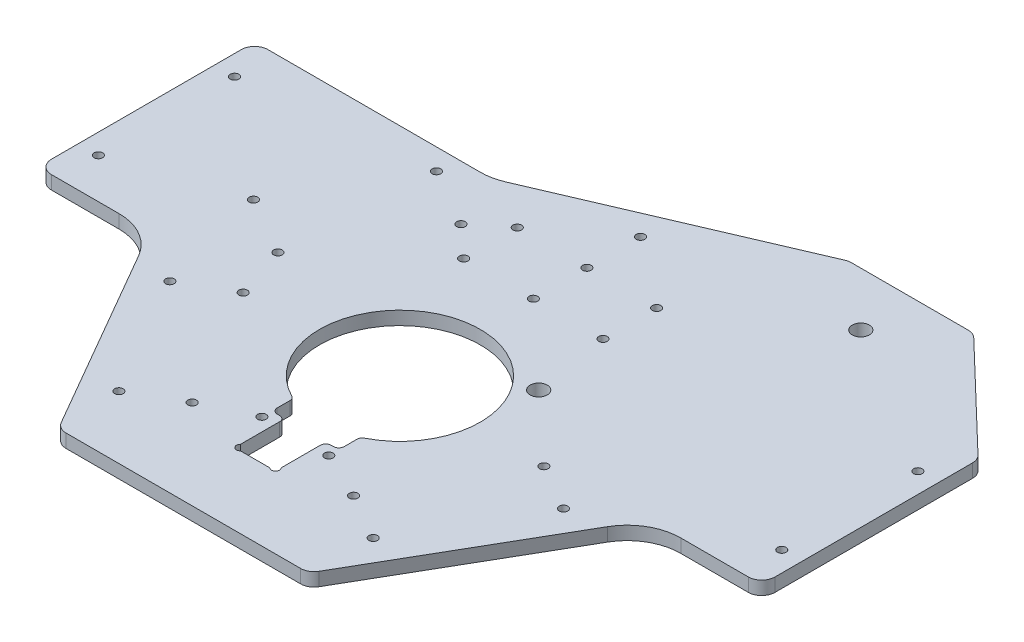
SolidWorks part; units mm, degrees
material "Acrylic (Medium-high impact)"
ref_plane "Front Plane" through (0, 0, 0) normal (0, 0, 1) x (1, 0, 0)
ref_plane "Top Plane" through (0, 0, 0) normal (0, 1, 0) x (1, 0, 0)
ref_plane "Right Plane" through (0, 0, 0) normal (1, 0, 0) x (0, 0, -1)
sketch "Sketch1" plane through (0, 0, 0) normal (0, 1, 0) x (1, 0, 0)
  line L0 (0, 0) -> (0, 59.7887) construction
  line L1 (88.7366, -45.4586) -> (19.8205, -5.6699) construction
  line L2 (-5, 99.5775) -> (5, 99.5775) construction
  line L3 (-5, 99.5775) -> (-5, 20) construction
  line L4 (-5, 20) -> (5, 20) construction
  line L5 (5, 99.5775) -> (5, 20) construction
  line L6 (-5, 99.5775) -> (5, 20) construction
  line L7 (-5, 20) -> (5, 99.5775) construction
  line L8 (88.7366, -45.4586) -> (83.7366, -54.1189) construction
  line L9 (83.7366, -54.1189) -> (14.8205, -14.3301) construction
  line L10 (19.8205, -5.6699) -> (14.8205, -14.3301) construction
  line L11 (-83.7366, -54.1189) -> (-14.8205, -14.3301) construction
  line L12 (-83.7366, -54.1189) -> (-88.7366, -45.4586) construction
  line L13 (-88.7366, -45.4586) -> (-19.8205, -5.6699) construction
  line L14 (-14.8205, -14.3301) -> (-19.8205, -5.6699) construction
  line L15 (-5, 59.7887) -> (-120, 59.7887) construction
  line L16 (-49.2786, -34.2245) -> (8.2214, -133.8174) construction
  line L23 (54.2786, -25.5642) -> (111.7786, 74.0287) construction
  circle A0 centre (0, 0) radius 20 construction
  circle A1 centre (-12.5, -19.3067) radius 3 construction
  circle A2 centre (12.5, -19.3067) radius 3 construction
  point P19 (0, 0)
  dimension "D1" = 40
  dimension "D6" = 6
  dimension "D7" = 25
  dimension "D2" = 79.5775
  dimension "D3" = 10
  dimension "D5" = 115
  dimension "D4" = 3
sketch "Sketch2" plane through (0, 0, 0) normal (0, 1, 0) x (1, 0, 0)
  line L0 (-5, 20) -> (5, 99.5775) construction
  line L1 (-26, 49.7887) -> (26, 49.7887) construction
  line L2 (-26, 49.7887) -> (-26, 69.7887) construction
  line L3 (-26, 69.7887) -> (26, 69.7887) construction
  line L4 (26, 49.7887) -> (26, 69.7887) construction
  line L5 (-26, 49.7887) -> (26, 69.7887) construction
  line L6 (-26, 69.7887) -> (26, 49.7887) construction
  line L8 (46.6434, 80.7887) -> (-46.6434, 80.7887)
  line L9 (-46.6434, 80.7887) -> (-93.2868, 0)
  line L10 (-93.2868, 0) -> (-46.6434, -80.7887)
  line L11 (-46.6434, -80.7887) -> (46.6434, -80.7887)
  line L12 (46.6434, -80.7887) -> (93.2868, 0)
  line L13 (93.2868, 0) -> (46.6434, 80.7887)
  circle A0 centre (26, 69.7887) radius 1.6
  circle A1 centre (26, 49.7887) radius 1.6
  circle A2 centre (-26, 49.7887) radius 1.6
  circle A3 centre (-26, 69.7887) radius 1.6
  circle A4 centre (0, 0) radius 30
  circle A5 centre (0, 0) radius 80.7887 construction
  circle A6 centre (56.1183, -2.3777) radius 1.6
  circle A7 centre (73.4388, -12.3777) radius 1.6
  circle A8 centre (47.4388, -57.411) radius 1.6
  circle A9 centre (30.1183, -47.411) radius 1.6
  circle A10 centre (-30.1183, -47.411) radius 1.6
  circle A11 centre (-47.4388, -57.411) radius 1.6
  circle A12 centre (-73.4388, -12.3777) radius 1.6
  circle A13 centre (-56.1183, -2.3777) radius 1.6
  point P0 (0, 59.7887)
  point P39 (0, 0)
  dimension "D3" = 3.2
  dimension "D4" = 60
  dimension "D5" = 11
  dimension "D1" = 52
  dimension "D2" = 20
  dimension "D6" = 3
extrude "Boss-Extrude1" add sketch "Sketch2" along normal blind 5
sketch "Sketch3" plane through (0, 0, 0) normal (0, 1, 0) x (1, 0, 0)
  line L0 (18, 80.7887) -> (18, 24) construction
  line L1 (46.6434, 80.7887) -> (-46.6434, 80.7887) construction
  line L2 (5, 99.5775) -> (5, 20) construction
  line L3 (85.9256, 92.2887) -> (41.3253, 15.0387) construction
  line L5 (26, 49.7887) -> (30.5, 49.7887) construction
  line L6 (30.5, 33.7887) -> (30.5, 49.7887) construction
  line L8 (46.6434, 120.7887) -> (93.2868, 120.7887)
  line L9 (93.2868, 120.7887) -> (93.2868, 0)
  line L14 (93.2868, 0) -> (46.6434, 80.7887) construction
  line L15 (93.2868, 0) -> (46.6434, 80.7887)
  line L16 (-46.6434, 80.7887) -> (46.6434, 120.7887)
  line L17 (46.6434, 120.7887) -> (46.6434, 80.7887) construction
  line L18 (46.6434, 80.7887) -> (-46.6434, 80.7887)
  line L19 (46.6434, -80.7887) -> (93.2868, 0) construction
  circle A0 centre (0, 0) radius 30 construction
  circle A1 centre (30.5, 21.2887) radius 12.5 construction
  circle A5 centre (71.2032, 100.7887) radius 3.2
  circle A6 centre (71.2032, 100.7887) radius 20 construction
  circle A7 centre (71.2032, 100.7887) radius 17 construction
  point P19 (85.9256, 92.2887)
  point P32 (69.9651, 120.7887)
  dimension "D2" = 25
  dimension "D3" = 16
  dimension "D4" = 6.4
  dimension "D5" = 20
  dimension "D6" = 34
  dimension "D1" = 13
extrude "Boss-Extrude2" add sketch "Sketch3" along normal up to surface (5 mm away) up to face at (-30.1183, 5, 49.011)
sketch "Sketch4" plane through (0, 5, 0) normal (0, 1, 0) x (1, 0, 0)
  circle A0 centre (30.5, 21.2887) radius 3.2
  dimension "D1" = 6.4
extrude "Cut-Extrude1" cut sketch "Sketch4" against normal through all
sketch "Sketch5" plane through (0, 5, 0) normal (0, 1, 0) x (1, 0, 0)
  line L4 (-7.6, -29.0214) -> (7.6, -29.0214)
  line L5 (-7.6, -29.0214) -> (-7.6, -54.0214)
  line L6 (-7.6, -54.0214) -> (7.6, -54.0214)
  line L7 (7.6, -29.0214) -> (7.6, -54.0214)
  circle A2 centre (0, 0) radius 30 construction
  dimension "D1" = 15.2
  dimension "D2" = 25
extrude "Cut-Extrude2" cut sketch "Sketch5" against normal through all
sketch "Sketch7" plane through (0, 0, 0) normal (0, -1, 0) x (1, 0, 0)
  line L0 (0, 0) -> (0, 39.0214) construction
  line L1 (0, 39.0214) -> (12.5, 39.0214) construction
  line L2 (0, 39.0214) -> (-12.5, 39.0214) construction
  line L3 (-7.6, 52.9607) -> (-6.5393, 52.9607) construction
  line L4 (-7.6, 29.0214) -> (-7.6, 54.0214) construction
  line L5 (-6.5393, 52.9607) -> (-6.5393, 54.0214) construction
  line L6 (-7.6, 54.0214) -> (7.6, 54.0214) construction
  line L7 (6.5393, 54.0214) -> (6.5393, 52.9607) construction
  line L8 (6.5393, 52.9607) -> (7.6, 52.9607) construction
  line L9 (7.6, 54.0214) -> (7.6, 29.0214) construction
  line L11 (-12.5, 35.2718) -> (12.5, 35.2718)
  line L12 (-12.5, 35.2718) -> (-12.5, 27.2718)
  line L13 (-12.5, 27.2718) -> (12.5, 27.2718)
  line L14 (12.5, 35.2718) -> (12.5, 27.2718)
  line L15 (-12.5, 35.2718) -> (12.5, 27.2718) construction
  line L16 (-12.5, 27.2718) -> (12.5, 35.2718) construction
  circle A0 centre (-12.5, 39.0214) radius 1.6
  circle A1 centre (12.5, 39.0214) radius 1.6
  circle A2 centre (-6.5393, 52.9607) radius 1.5
  circle A3 centre (6.5393, 52.9607) radius 1.5
  arc A4 (-7.6, 29.0214) -> (7.6, 29.0214) centre (0, 0) ccw construction
  point P24 (0, 31.2718)
  dimension "D1" = 25
  dimension "D3" = 3.2
  dimension "D4" = 3
  dimension "D2" = 39.0214
  dimension "D5" = 25
  dimension "D6" = 8
extrude "Cut-Extrude3" cut sketch "Sketch7" against normal through all
sketch "Sketch8" plane through (0, 0, 0) normal (0, 1, 0) x (1, 0, 0)
  line L0 (-93.2868, 0) -> (-135, 0)
  line L1 (-135, 0) -> (-135, 80.7887)
  line L2 (-135, 80.7887) -> (-46.6434, 80.7887)
  line L3 (-93.2868, 0) -> (-46.6434, 80.7887)
  line L4 (93.2868, 0) -> (135, 0)
  line L5 (135, 0) -> (135, 80.7887)
  line L6 (135, 80.7887) -> (93.2868, 120.7887)
  line L7 (93.2868, 0) -> (93.2868, 120.7887)
  dimension "D1" = 270
extrude "Boss-Extrude3" add sketch "Sketch8" along normal up to surface (5 mm away) up to face at (12.5, 5, 37.4214)
sketch "Sketch9" plane through (0, 0, 0) normal (0, -1, 0) x (1, 0, 0)
  line L0 (135, 0) -> (135, -80.7887) construction
  circle A0 centre (-37.6014, -60.3916) radius 1.6
  circle A1 centre (-59.252, -72.8916) radius 1.6
  circle A2 centre (-84.252, -29.5904) radius 1.6
  circle A3 centre (-62.6014, -17.0904) radius 1.6
  circle A4 centre (0, -49.7887) radius 1.6
  circle A5 centre (0, -69.7887) radius 1.6
  circle A6 centre (0, -89.7887) radius 1.6
  circle A7 centre (127.5, -65.79) radius 1.6
  circle A8 centre (127.5, -15) radius 1.6
  circle A9 centre (-127.5, -14.9987) radius 1.6
  circle A10 centre (-127.5, -65.7887) radius 1.6
  dimension "D1" = 3.2
  dimension "D2" = 7.5
  dimension "D3" = 135
  dimension "D4" = 172.6014
  dimension "D5" = 194.252
  dimension "D6" = 197.6014
  dimension "D7" = 219.252
  dimension "D8" = 262.5
  dimension "D9" = 95.7875
  dimension "D10" = 95.7887
  dimension "D11" = 97.8791
  dimension "D12" = 110.3791
  dimension "D13" = 130.5775
  dimension "D14" = 141.1804
  dimension "D15" = 146.5775
  dimension "D16" = 146.5787
  dimension "D17" = 150.5775
  dimension "D18" = 153.6804
  dimension "D19" = 170.5775
extrude "Cut-Extrude4" cut sketch "Sketch9" against normal through all
fillet "Fillet1" radius 5 8 edges at (46.6434, 2.5, 80.7887) (-46.6434, 2.5, 80.7887) (-135, 2.5, -80.7887) (46.6434, 2.5, -120.7887) (93.2868, 2.5, -120.7887) (135, 2.5, -80.7887) (135, 2.5, 0) (-135, 2.5, 0)
fillet "Fillet2" radius 20 3 edges at (-46.6434, 2.5, -80.7887) (93.2868, 2.5, 0) (-93.2868, 2.5, 0)
fillet "Fillet3" radius 2 6 edges at (12.5, 2.5, 27.2718) (12.5, 2.5, 35.2718) (7.6, 2.5, 35.2718) (-7.6, 2.5, 35.2718) (-12.5, 2.5, 35.2718) (-12.5, 2.5, 27.2718)
